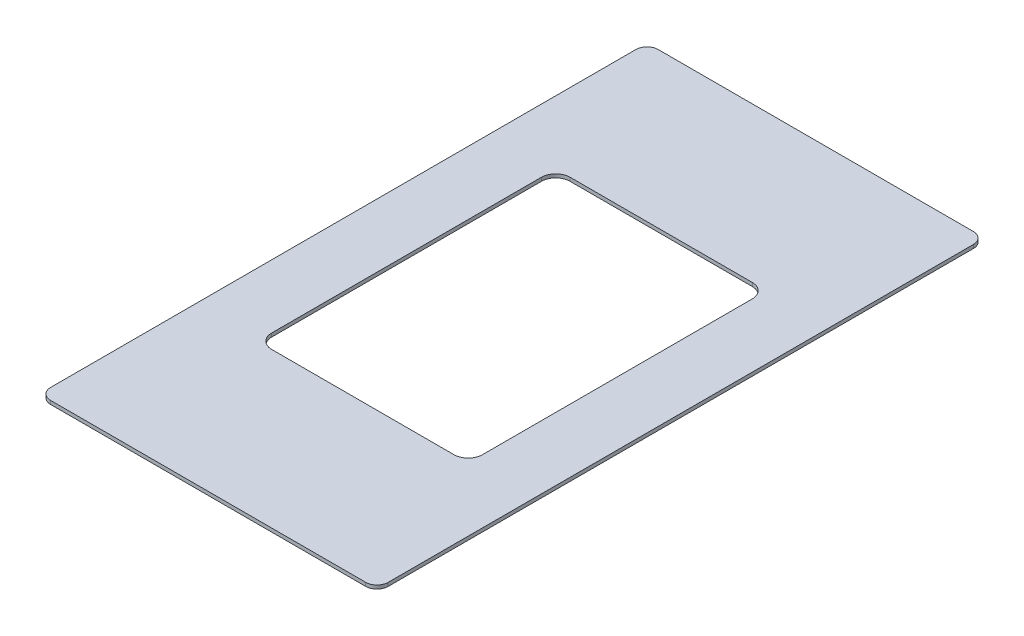
SolidWorks part; units mm, degrees
material "5052-H32"
ref_plane "Front Plane" through (0, 0, 0) normal (0, 0, 1) x (1, 0, 0)
ref_plane "Top Plane" through (0, 0, 0) normal (0, 1, 0) x (1, 0, 0)
ref_plane "Right Plane" through (0, 0, 0) normal (1, 0, 0) x (0, 0, -1)
sketch "Sketch9" plane through (0, 0, 0) normal (0, 1, 0) x (1, 0, 0)
  line L0 (-130, 0) -> (130, 0) construction
  line L1 (-130, 500) -> (130, 500) construction
  line L2 (-130, 500) -> (-130, 0) construction
  line L4 (130, 500) -> (130, 0) construction
  line L13 (0, 250) -> (0, 520) construction
  line L14 (93.6625, 117.4438) -> (-93.6625, 117.4437)
  line L15 (-150, 520) -> (150, 520)
  line L16 (150, 520) -> (150, -20)
  line L17 (-150, -20) -> (150, -20)
  line L18 (-150, 520) -> (-150, -20)
  line L19 (0, 250) -> (150, 250) construction
  line L20 (93.6625, 117.4438) -> (93.6625, 382.5562)
  line L21 (93.6625, 382.5562) -> (-93.6625, 382.5562)
  line L22 (-93.6625, 117.4437) -> (-93.6625, 382.5562)
  line L23 (93.6625, 117.4438) -> (-93.6625, 382.5562) construction
  line L24 (93.6625, 382.5562) -> (-93.6625, 117.4437) construction
  line L25 (-130, 0) -> (130, 0) construction
  point P5 (0, 250)
  point P19 (0, 0)
  dimension "D10" = 500
  dimension "D9" = 260
  dimension "D3" = 265.1125
  dimension "D4" = 187.325
  dimension "D2" = 20
extrude "Boss-Extrude7" add sketch "Sketch9" along normal blind 3.175 separate body contours L15 L18 L17 L16 region at (0, 0, -513.8226)
fillet "Fillet4" radius 10 4 edges at (-150, 1.5875, -520) (150, 1.5875, -520) (-150, 1.5875, 20) (150, 1.5875, 20)
sketch "Sketch10" plane through (0, 0, 0) normal (0, 1, 0) x (1, 0, 0)
  line L0 (0, 0) -> (0, 500) construction
  line L1 (-130, 500) -> (130, 500) construction
  line L2 (-130, 500) -> (-130, 0) construction
  line L3 (-130, 0) -> (130, 0) construction
  line L4 (130, 500) -> (130, 0) construction
  line L8 (-150, 520) -> (-150, -20) construction
  line L9 (-150, -20) -> (150, -20) construction
  line L10 (150, 520) -> (150, -20) construction
  line L11 (-150, 520) -> (150, 520) construction
  line L15 (130, 250) -> (-130, 250) construction
  circle A0 centre (-140, -10) radius 2.5
  circle A2 centre (-140, 42) radius 2.5
  circle A3 centre (-140, 94) radius 2.5
  circle A4 centre (-140, 146) radius 2.5
  circle A5 centre (-140, 198) radius 2.5
  circle A6 centre (-140, 250) radius 2.5
  circle A7 centre (-140, 302) radius 2.5
  circle A8 centre (-140, 354) radius 2.5
  circle A9 centre (-140, 406) radius 2.5
  circle A10 centre (-140, 458) radius 2.5
  circle A16 centre (-140, 510) radius 2.5
  circle A17 centre (-83, 510) radius 2.5
  circle A18 centre (-26, 510) radius 2.5
  circle A19 centre (31, 510) radius 2.5
  circle A20 centre (88, 510) radius 2.5
  circle A21 centre (145, 510) radius 2.5
  circle A22 centre (145, 458) radius 2.5
  circle A23 centre (145, 406) radius 2.5
  circle A24 centre (145, 354) radius 2.5
  circle A25 centre (145, 302) radius 2.5
  circle A26 centre (145, 250) radius 2.5
  circle A27 centre (145, 198) radius 2.5
  circle A28 centre (145, 146) radius 2.5
  circle A29 centre (145, 94) radius 2.5
  circle A30 centre (145, 42) radius 2.5
  circle A31 centre (145, -10) radius 2.5
  circle A38 centre (89, -10) radius 2.5
  circle A39 centre (33, -10) radius 2.5
  circle A40 centre (-23, -10) radius 2.5
  circle A41 centre (-79, -10) radius 2.5
  dimension "D4" = 5
  dimension "D7" = 5
  dimension "D2" = 10
  dimension "D3" = 10
  dimension "D5" = 6
  dimension "D6" = 11
  dimension "D8" = 11
  dimension "D9" = 260
  dimension "D1" = 20
fillet "Fillet5" radius 12.7 4 edges at (-93.6625, 1.5875, -117.4437) (93.6625, 1.5875, -117.4438) (93.6625, 1.5875, -382.5562) (-93.6625, 1.5875, -382.5562)
extrude "Bolt Holes" [suppressed] cut sketch "Sketch10" along normal up to next
equation "\"W\"= 260"
equation "\"D9@Sketch9\"=\"W\""
equation "\"L\"=500"
equation "\"D10@Sketch9\"=\"L\""
